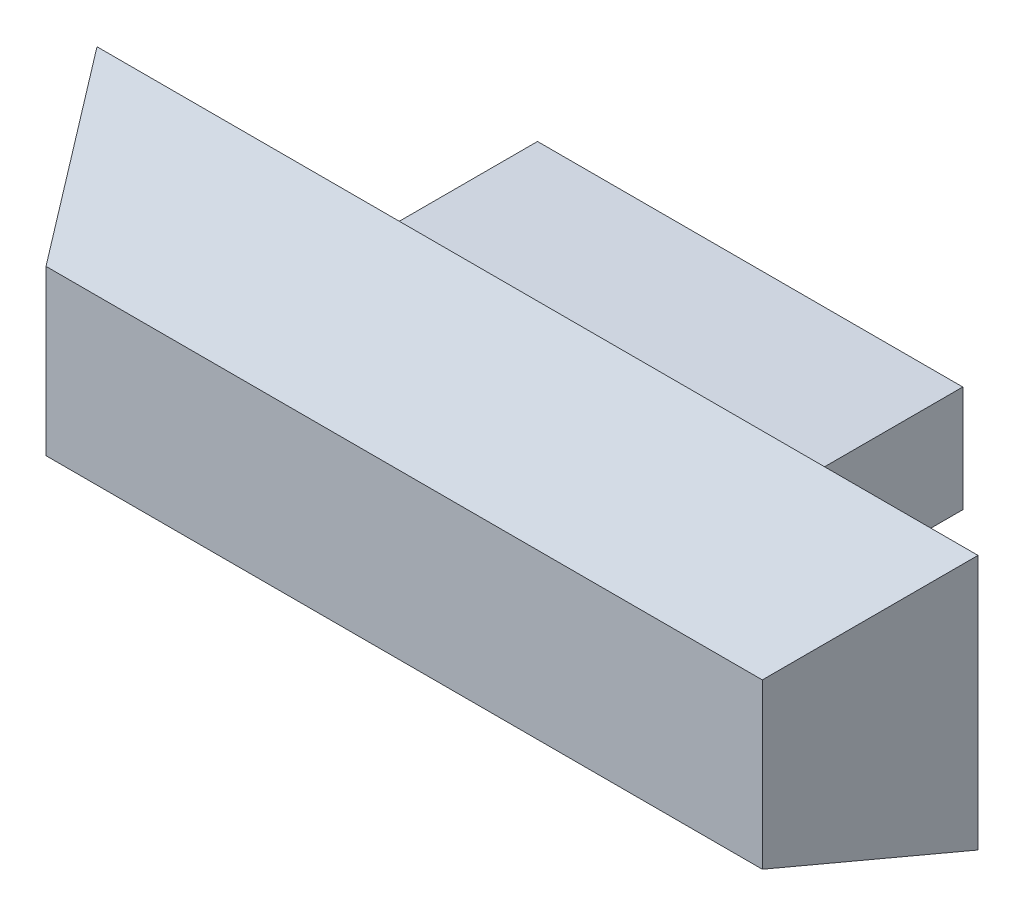
SolidWorks part; units mm, degrees
material "PET"
ref_plane "Front Plane" through (0, 0, 0) normal (0, 0, 1) x (1, 0, 0)
ref_plane "Top Plane" through (0, 0, 0) normal (0, 1, 0) x (1, 0, 0)
ref_plane "Right Plane" through (0, 0, 0) normal (1, 0, 0) x (0, 0, -1)
sketch "Sketch1" plane through (0, 0, 0) normal (0, 0, 1) x (1, 0, 0)
  line L1 (83.5025, 67.437) -> (70.3473, 67.437)
  line L2 (83.5025, 67.437) -> (83.5025, 63.627)
  line L3 (83.5025, 63.627) -> (70.3473, 63.627)
  line L4 (70.3473, 67.437) -> (70.3473, 63.627)
  point P8 (83.5025, 67.437)
  dimension "D1" = 3.81
  dimension "D2" = 13.1552
extrude "Boss-Extrude1" add sketch "Sketch1" along normal blind 2.54
chamfer "Chamfer1" distance 2.54 angle 35 1 edges at (70.3473, 65.532, 2.54) first distance on face at (70.3473, 65.532, 1.27)
chamfer "Chamfer2" distance 2.54 angle 15 3 edges at (77.8142, 63.627, 2.54) (83.5025, 65.532, 2.54) (77.8142, 67.437, 2.54) first distance on face at (77.3695, 63.627, 1.27) first distance on face at (83.5025, 65.532, 1.27) first distance on face at (77.3695, 67.437, 1.27)
sketch "Sketch2" plane through (0, 0, 0) normal (0, 0, -1) x (-1, 0, 0)
  line L0 (-70.3473, 65.532) -> (-83.5025, 65.532) construction
  line L3 (-70.3473, 67.437) -> (-70.3473, 63.627) construction
  line L8 (-83.5025, 63.627) -> (-83.5025, 67.437) construction
  line L10 (-80.0999, 66.3258) -> (-73.7499, 66.3258)
  line L11 (-80.0999, 66.3258) -> (-80.0999, 64.7383)
  line L12 (-80.0999, 64.7383) -> (-73.7499, 64.7383)
  line L13 (-73.7499, 66.3258) -> (-73.7499, 64.7383)
  line L14 (-80.0999, 66.3258) -> (-73.7499, 64.7383) construction
  line L15 (-80.0999, 64.7383) -> (-73.7499, 66.3258) construction
  point P6 (-76.9249, 65.532)
  dimension "D1" = 6.35
  dimension "D2" = 1.5875
extrude "Boss-Extrude3" add sketch "Sketch2" along normal blind 3.175
